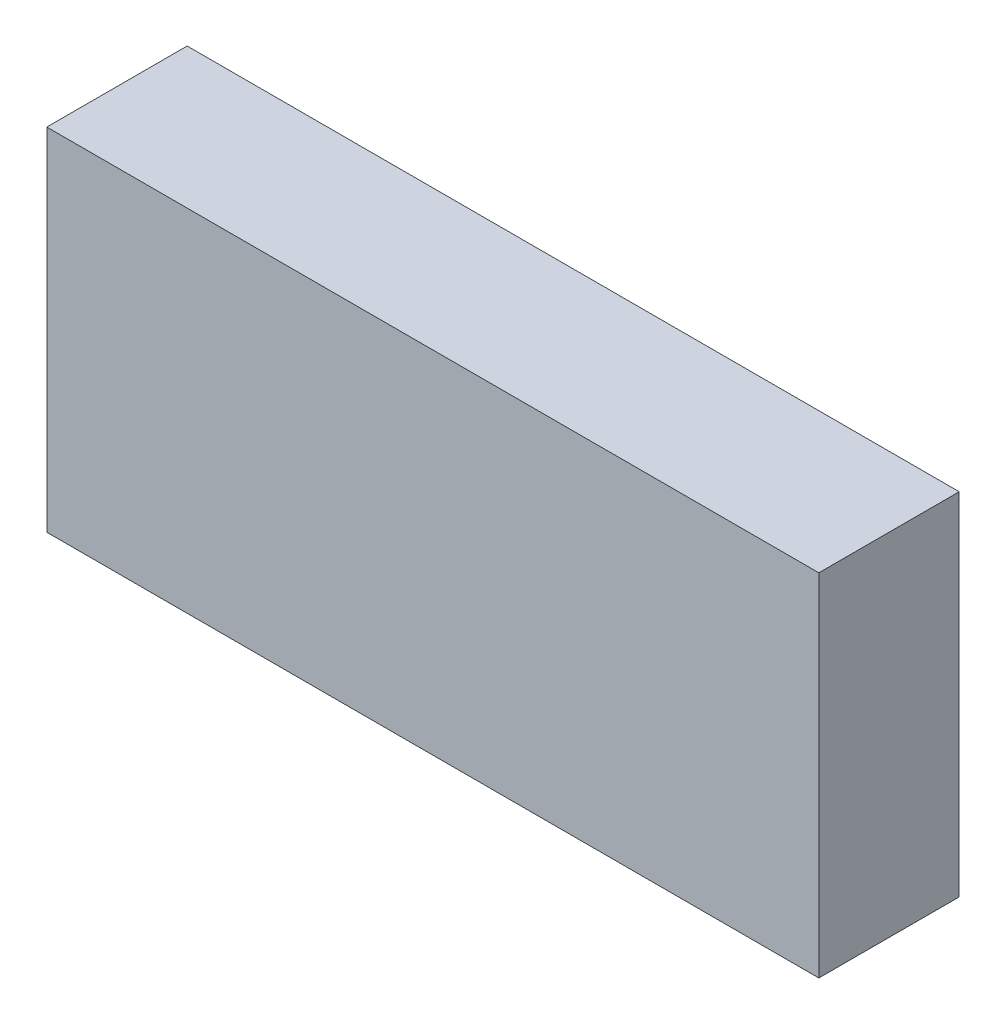
SolidWorks part; units mm, degrees
ref_plane "Front Plane" through (0, 0, 0) normal (0, 0, 1) x (1, 0, 0)
ref_plane "Top Plane" through (0, 0, 0) normal (0, 1, 0) x (1, 0, 0)
ref_plane "Right Plane" through (0, 0, 0) normal (1, 0, 0) x (0, 0, -1)
sketch "Sketch1" plane through (0, 0, 0) normal (0, 1, 0) x (1, 0, 0)
  line L1 (-19.5, 77.5) -> (19.5, 77.5)
  line L2 (-19.5, 77.5) -> (-19.5, -77.5)
  line L3 (-19.5, -77.5) -> (19.5, -77.5)
  line L4 (19.5, 77.5) -> (19.5, -77.5)
  line L5 (-19.5, 77.5) -> (19.5, -77.5) construction
  line L6 (-19.5, -77.5) -> (19.5, 77.5) construction
  point P0 (0, 0)
  dimension "D1" = 39
  dimension "D2" = 155
extrude "Boss-Extrude1" add sketch "Sketch1" along normal blind 2
sketch "Sketch2" plane through (0, 2, 0) normal (0, 1, 0) x (1, 0, 0)
  line L0 (-17.5, -75.5) -> (-17.5, -77.5)
  line L1 (-19.5, 77.5) -> (19.5, 77.5)
  line L2 (-19.5, 77.5) -> (-19.5, -77.5)
  line L3 (-19.5, -77.5) -> (19.5, -77.5)
  line L4 (19.5, 77.5) -> (19.5, -77.5)
  line L5 (-17.5, 75.5) -> (17.5, 75.5)
  line L6 (-17.5, 75.5) -> (-17.5, -75.5)
  line L7 (-17.5, -75.5) -> (17.5, -75.5)
  line L8 (17.5, 75.5) -> (17.5, -75.5)
  line L9 (-17.5, 75.5) -> (17.5, -75.5) construction
  line L10 (-17.5, -75.5) -> (17.5, 75.5) construction
  line L11 (17.5, -75.5) -> (17.5, -77.5)
  point P6 (0, 0)
  line M9 (19.5, -77.5) -> (19.5, 77.5)
  line M10 (19.5, 77.5) -> (-19.5, 77.5)
  line M11 (-19.5, 77.5) -> (-19.5, -77.5)
  line M12 (-19.5, -77.5) -> (19.5, -77.5)
  dimension "D1" = 2
  dimension "D2" = 2
extrude "Boss-Extrude2" add sketch "Sketch2" along normal blind 38 contours L8 L11 L3 L0 L6 L5 M9 M10 M11 M12 region at (-19.0983, 2, 76.5)
sketch "Sketch3" plane through (0, 2, 0) normal (0, 1, 0) x (1, 0, 0)
  line L0 (-17.5, 75.5) -> (-17.5, -77.5) construction
  line L1 (-17.5, -77.5) -> (-15.5, -77.5)
  line L2 (-17.5, -77.5) -> (-17.5, -75.5)
  line L3 (-17.5, -75.5) -> (-15.5, -75.5)
  line L4 (-15.5, -77.5) -> (-15.5, -75.5)
  line L5 (-17.5, -73.3) -> (-15.5, -73.3)
  line L6 (-17.5, -73.3) -> (-17.5, -71.3)
  line L7 (-17.5, -71.3) -> (-15.5, -71.3)
  line L8 (-15.5, -73.3) -> (-15.5, -71.3)
  line L9 (17.5, 75.5) -> (17.5, -77.5) construction
  line L10 (17.5, -77.5) -> (15.5, -77.5)
  line L11 (17.5, -77.5) -> (17.5, -75.5)
  line L12 (17.5, -75.5) -> (15.5, -75.5)
  line L13 (15.5, -77.5) -> (15.5, -75.5)
  line L14 (17.5, -73.3) -> (15.5, -73.3)
  line L15 (17.5, -73.3) -> (17.5, -71.3)
  line L16 (17.5, -71.3) -> (15.5, -71.3)
  line L17 (15.5, -73.3) -> (15.5, -71.3)
  line L18 (15.5, -75.5) -> (15.5, -73.3) construction
  line L19 (-15.5, -73.3) -> (15.5, -73.3) construction
  line L20 (-15.5, -75.5) -> (-15.5, -73.3) construction
  line L21 (-15.5, -75.5) -> (15.5, -75.5) construction
  line L22 (15.5, -71.3) -> (-15.5, -71.3) construction
  dimension "D1" = 2
  dimension "D2" = 2
  dimension "D3" = 2.2
  dimension "D4" = 2
extrude "Boss-Extrude3" add sketch "Sketch3" along normal up to surface (38 mm away) up to face at (0, 40, 0.5)
sketch "Sketch4" plane through (0, 0, -75.5) normal (0, 0, 1) x (1, 0, 0)
  line L0 (-17.5, 40) -> (-15.5, 40)
  line L1 (-17.5, 40) -> (17.5, 40) construction
  line L2 (-15.5, 40) -> (-15.5, 38)
  line L3 (-15.5, 38) -> (-17.5, 38)
  line L5 (-17.5, 38) -> (-17.5, 40)
  line L7 (-17.5, 40) -> (-17.5, 2) construction
  line L8 (-15.5, 33.8) -> (-17.5, 31.8)
  line L9 (-17.5, 31.8) -> (-17.5, 35.8)
  line L10 (-15.5, 33.8) -> (-15.5, 35.8)
  line L11 (-15.5, 35.8) -> (-17.5, 35.8)
  line L12 (0, 0) -> (0, 40) construction
  line L13 (15.5, 35.8) -> (17.5, 35.8)
  line L14 (15.5, 33.8) -> (15.5, 35.8)
  line L15 (17.5, 31.8) -> (17.5, 35.8)
  line L16 (15.5, 33.8) -> (17.5, 31.8)
  line L17 (17.5, 38) -> (17.5, 40)
  line L18 (15.5, 38) -> (17.5, 38)
  line L19 (15.5, 40) -> (15.5, 38)
  line L20 (17.5, 40) -> (15.5, 40)
  dimension "D1" = 2
  dimension "D2" = 2
  dimension "D3" = 45
  dimension "D4" = 2.2
  dimension "D5" = 2
extrude "Boss-Extrude4" add sketch "Sketch4" along normal up to surface (153 mm away) up to face at (0, 20.5, 77.5)
sketch "Sketch5" plane through (0, 2, 0) normal (0, 1, 0) x (1, 0, 0)
  line L1 (-15.5, -77.5) -> (15.5, -77.5)
  line L2 (-15.5, -77.5) -> (-15.5, -75.5)
  line L3 (-15.5, -75.5) -> (15.5, -75.5)
  line L4 (15.5, -77.5) -> (15.5, -75.5)
  line L5 (-15.5, -71.3) -> (15.5, -71.3)
  line L6 (-15.5, -71.3) -> (-15.5, -73.3)
  line L7 (-15.5, -73.3) -> (15.5, -73.3)
  line L8 (15.5, -71.3) -> (15.5, -73.3)
sketch "Sketch6" plane through (0, 0, -75.5) normal (0, 0, 1) x (1, 0, 0)
  line L0 (-17.5, 38) -> (-15.5, 38) construction
  line L1 (-17.5, 38) -> (17.5, 38)
  line L2 (-17.5, 38) -> (-17.5, 35.8)
  line L3 (-17.5, 35.8) -> (17.5, 35.8)
  line L4 (17.5, 38) -> (17.5, 35.8)
  line L5 (-17.5, 38) -> (-17.5, 35.8) construction
  line L6 (-15.5, 35.8) -> (-17.5, 35.8) construction
extrude "Cut-Extrude1" cut sketch "Sketch6" along normal through all
sketch "Sketch7" plane through (0, 2, 0) normal (0, 1, 0) x (1, 0, 0)
  line L1 (-17.5, -75.5) -> (17.5, -75.5)
  line L2 (-17.5, -75.5) -> (-17.5, -73.3)
  line L3 (-17.5, -73.3) -> (17.5, -73.3)
  line L4 (17.5, -75.5) -> (17.5, -73.3)
extrude "Cut-Extrude2" cut sketch "Sketch7" along normal through all
extrude "Boss-Extrude5" add sketch "Sketch5" along normal blind 2
sketch "Sketch8" plane through (0, 0, 0) normal (1, 0, 0) x (0, 0, -1)
  line L0 (75.5, 40) -> (73.5, 40)
  line L1 (-73.3, 40) -> (75.5, 40) construction
  line L2 (73.5, 40) -> (73.5, 38)
  line L3 (-73.3, 38) -> (75.5, 38) construction
  line L4 (73.5, 38) -> (75.5, 38)
  line L5 (75.5, 38) -> (75.5, 40)
  line L6 (75.5, 35.8) -> (73.5, 35.8)
  line L7 (-73.3, 35.8) -> (75.5, 35.8) construction
  line L8 (73.5, 35.8) -> (73.5, 33.8)
  line L9 (-71.3, 33.8) -> (75.5, 33.8) construction
  line L10 (73.5, 33.8) -> (75.5, 31.8)
  line L11 (75.5, 31.8) -> (75.5, 35.8)
  dimension "D1" = 2
extrude "Boss-Extrude6" add sketch "Sketch8" along normal up to surface and the other way up to surface up to face at (17.5, 16.9, -2.1) other way up to face at (-17.5, 16.9, -2.1)
sketch "Sketch10" plane through (-17.5, 0, 0) normal (1, 0, 0) x (0, 0, -1)
  line L1 (-75.5, 35.8) -> (-77.5, 35.8)
  line L2 (-75.5, 35.8) -> (-75.5, 38)
  line L3 (-75.5, 38) -> (-77.5, 38)
  line L4 (-77.5, 35.8) -> (-77.5, 38)
  line L5 (-73.3, 40) -> (-75.5, 40)
  line L6 (-73.3, 40) -> (-73.3, 38)
  line L7 (-73.3, 38) -> (-75.5, 38)
  line L8 (-75.5, 40) -> (-75.5, 38)
  line M1 (-75.5, 40) -> (-75.5, 38)
  line M2 (-75.5, 38) -> (-77.5, 38)
  line M3 (-77.5, 38) -> (-77.5, 35.8)
  line M4 (-77.5, 35.8) -> (-75.5, 35.8)
  line M11 (-73.3, 38) -> (-73.3, 40)
  line M12 (-73.3, 40) -> (-75.5, 40)
extrude "Boss-Extrude8" add sketch "Sketch10" along normal up to surface (2 mm away) contours L2 M4 M2 M3 | L7 M11 M12 M1 region at (-17.5, 39, 74.4) region at (-17.5, 36.9, 76.5) up to face at (-15.5, 39, -0.1)
sketch "Sketch11" plane through (17.5, 0, 0) normal (-1, 0, 0) x (0, 0, 1)
  line L1 (75.5, 35.8) -> (77.5, 35.8)
  line L2 (75.5, 35.8) -> (75.5, 38)
  line L3 (75.5, 38) -> (77.5, 38)
  line L4 (77.5, 35.8) -> (77.5, 38)
  line L5 (73.3, 40) -> (75.5, 40)
  line L6 (73.3, 40) -> (73.3, 38)
  line L7 (73.3, 38) -> (75.5, 38)
  line L8 (75.5, 40) -> (75.5, 38)
  line M2 (75.5, 35.8) -> (77.5, 35.8)
  line M3 (77.5, 35.8) -> (77.5, 38)
  line M4 (77.5, 38) -> (75.5, 38)
  line M5 (75.5, 38) -> (75.5, 40)
  line M6 (75.5, 40) -> (73.3, 40)
  line M7 (73.3, 40) -> (73.3, 38)
extrude "Boss-Extrude9" add sketch "Sketch11" along normal up to surface (2 mm away) contours L2 M2 M3 M4 | L7 M7 M5 M6 region at (17.5, 36.9, 76.5) region at (17.5, 39, 74.4) up to face at (15.5, 39, -0.1)
fillet "Fillet2" radius 2.5 17 edges at (-17.5, 16.9, 71.3) (17.5, 16.9, 71.3) (19.5, 20, 77.5) (-19.5, 20, 77.5) (-19.5, 20, -77.5) (-17.5, 16.9, -75.5) (17.5, 16.9, -75.5) (19.5, 20, -77.5) (-19.5, 40, 0) (0, 40, -77.5) (19.5, 40, 0) (0, 0, -77.5) (0, 0, 77.5) (-19.5, 0, 0) (19.5, 0, 0) (-17.5, 40, 77.5) (17.5, 40, 77.5)
sketch "Sketch13" plane through (0, 0, -77.5) normal (0, 0, -1) x (-1, 0, 0)
  line L0 (15.5, 37.5) -> (15.5, 4) construction
  line L1 (-15.5, 7) -> (15.5, 7)
  line L2 (-15.5, 7) -> (-15.5, 4)
  line L3 (-15.5, 4) -> (15.5, 4)
  line L4 (15.5, 7) -> (15.5, 4)
  dimension "D1" = 3
sketch "Sketch14" plane through (0, 0, -75.5) normal (0, 0, 1) x (1, 0, 0)
  line L1 (-18.25, 9) -> (18.25, 9)
  line L2 (-18.25, 9) -> (-18.25, 1.25)
  line L3 (-18.25, 1.25) -> (18.25, 1.25)
  line L4 (18.25, 9) -> (18.25, 1.25)
  line L5 (15.5, 7) -> (-15.5, 7) construction
  line L7 (17, 0) -> (17, 2.5) construction
  line L8 (19.5, 2.5) -> (17, 2.5) construction
  line L10 (-19.5, 2.5) -> (-17, 2.5) construction
  point P20 (17, 1.25)
  point P23 (18.25, 2.5)
  point P26 (-18.25, 2.5)
  dimension "D1" = 2
extrude "Boss-Extrude10" add sketch "Sketch14" along normal blind 2
extrude "Cut-Extrude4" cut sketch "Sketch13" against normal blind 2
fillet "Fillet3" radius 2 1 edges at (0, 9, -73.5)
fillet "Fillet4" radius 0.5 12 edges at (0, 4, -77.5) (0, 7, -77.5) (15.5, 7, -76.5) (15.5, 4, -76.5) (15.5, 5.5, -77.5) (-15.5, 4, -76.5) (-15.5, 7, -76.5) (-15.5, 5.5, -77.5) (0, 7, -75.5) (-15.5, 5.5, -75.5) (0, 4, -75.5) (15.5, 5.5, -75.5)
sketch "Sketch15" plane through (0, 0, 0) normal (0, -1, 0) x (1, 0, 0)
  line L0 (0, 77.5) -> (0, 0) construction
  line L1 (-17, 77.5) -> (17, 77.5) construction
  line L2 (0, 0) -> (0, -77.5) construction
  line L4 (17, -77.5) -> (-17, -77.5) construction
  circle A0 centre (0, 38.75) radius 5.1
  circle A1 centre (0, -38.75) radius 5.1
  dimension "D1" = 10.2
extrude "Cut-Extrude5" cut sketch "Sketch15" against normal through all
sketch "Sketch16" plane through (0, 2, 0) normal (0, 1, 0) x (1, 0, 0)
  circle A0 centre (0, 38.75) radius 7.1
  circle A1 centre (0, -38.75) radius 7.1
  circle A2 centre (0, 38.75) radius 5.1 construction
  dimension "D1" = 2
extrude "Boss-Extrude11" add sketch "Sketch16" along normal blind 1
fillet "Fillet5" radius 0.5 4 edges at (0, 2, 45.85) (0, 2, -31.65) (0, 3, 45.85) (0, 3, -31.65)
fillet "Fillet7" radius 0.5 8 edges at (15.5, 40, 0.75) (15.5, 39.2678, 76.7678) (-15.5, 40, 0.75) (-15.5, 39.2678, 76.7678) (0, 40, -73.5) (15.5, 20.75, 77.5) (-15.5, 20.75, 77.5) (0, 4, 77.5)
sketch "Sketch17" plane through (0, 0, 0) normal (0, -1, 0) x (1, 0, 0)
  line L0 (-17, -77.5) -> (-17, 70.3)
  line L1 (-17, -77.5) -> (17, -77.5)
  line L2 (17, -77.5) -> (17, 70.3)
  line L3 (17, -75) -> (17, 75) construction
  line L5 (17, 70.3) -> (15, 71.3)
  line L6 (15, 71.3) -> (15, 77.5)
  line L7 (15, 77.5) -> (-15, 77.5)
  line L8 (-15, 77.5) -> (-15, 71.3)
  line L9 (-15, 71.3) -> (-17, 70.3)
  line L10 (-17, 75) -> (-17, -75) construction
  line L12 (-15, 71.3) -> (15, 71.3) construction
  line L13 (17, 70.3) -> (-17, 70.3) construction
  line L14 (0, 71.3) -> (0, 77.5) construction
  line L15 (-17, 77.5) -> (17, 77.5) construction
  arc A0 (-19.5, -75) -> (-17, -77.5) centre (-17, -75) ccw construction
  dimension "D1" = 1
  dimension "D2" = 30
  dimension "D3" = 6.2
extrude "Cut-Extrude6" cut sketch "Sketch17" against normal blind 6
sketch "Sketch18" plane through (0, 0, 0) normal (0, 0, 1) x (1, 0, 0)
  line L0 (15, 9) -> (-15, 9) construction
  line L1 (-14.5, 9) -> (14.5, 9)
  line L2 (-14.5, 9) -> (-14.5, 6)
  line L3 (-14.5, 6) -> (14.5, 6)
  line L4 (14.5, 9) -> (14.5, 6)
  line L5 (-17, 6) -> (17, 6) construction
  line L6 (0, 6) -> (0, 0) construction
  dimension "D1" = 29
extrude "Cut-Extrude8" cut sketch "Sketch18" against normal through all
sketch "Sketch20" plane through (0, 0, 0) normal (0, 0, 1) x (1, 0, 0)
  line L0 (-16, 40) -> (16, 40) construction
  line L1 (-19.5, 40) -> (-14.5, 40)
  line L2 (-19.5, 40) -> (-19.5, 0)
  line L3 (-19.5, 0) -> (-14.5, 0)
  line L4 (-14.5, 40) -> (-14.5, 0)
  line L5 (-14.5, 6) -> (14.5, 6)
  line L6 (-14.5, 6) -> (-14.5, 40)
  line L7 (-14.5, 40) -> (14.5, 40)
  line L8 (14.5, 6) -> (14.5, 40)
  line L9 (14.5, 40) -> (19.5, 40)
  line L10 (14.5, 40) -> (14.5, 0)
  line L11 (14.5, 0) -> (19.5, 0)
  line L12 (19.5, 40) -> (19.5, 0)
  line L13 (-15, 0) -> (-17, 0) construction
  line L14 (-19.5, 2.5) -> (-19.5, 37.5) construction
  line L15 (17, 0) -> (15, 0) construction
  line L16 (19.5, 37.5) -> (19.5, 2.5) construction
extrude "Cut-Extrude11" cut sketch "Sketch20" against normal through all both and the other way through all contours L12 L9 L8 L10 L11 | L1 L2 L3 L4 region at (17, 20, 0)
sketch "Sketch21" plane through (0, 0, 0) normal (0, 0, 1) x (1, 0, 0)
  line L0 (14.5, 40) -> (-14.5, 40) construction
  line L1 (-14.5, 9) -> (14.5, 9)
  line L2 (-14.5, 9) -> (-14.5, 40)
  line L3 (-14.5, 40) -> (14.5, 40)
  line L4 (14.5, 9) -> (14.5, 40)
  line L5 (-14.5, 9) -> (14.5, 40) construction
  line L6 (-14.5, 40) -> (14.5, 9) construction
  line L8 (-5.5, 9) -> (5.5, 9)
  line L9 (-5.5, 9) -> (-5.5, 40)
  line L10 (-5.5, 40) -> (5.5, 40)
  line L11 (5.5, 9) -> (5.5, 40)
  line L12 (-5.5, 9) -> (5.5, 40) construction
  line L13 (-5.5, 40) -> (5.5, 9) construction
  point P0 (0, 24.5)
  point P7 (0, 24.5)
  dimension "D1" = 11
extrude "Cut-Extrude12" cut sketch "Sketch21" against normal through all contours L1 L9 L3 L2 | L11 L1 L4 L3 region at (-10, 24.5, 0) region at (10, 24.5, 0)
sketch "Sketch22" plane through (0, 0, -75.5) normal (0, 0, 1) x (1, 0, 0)
  line L1 (-5.5, 40) -> (5.5, 40)
  line L2 (-5.5, 40) -> (-5.5, 31.8)
  line L3 (-5.5, 31.8) -> (5.5, 31.8)
  line L4 (5.5, 40) -> (5.5, 31.8)
  line L5 (-5.5, 9) -> (5.5, 9)
  line L6 (-5.5, 9) -> (-5.5, 31.8)
  line L7 (-5.5, 31.8) -> (5.5, 31.8)
  line L8 (5.5, 9) -> (5.5, 31.8)
  line M1 (5.5, 31.8) -> (-5.5, 31.8)
extrude "Cut-Extrude13" cut sketch "Sketch22" against normal through all both and the other way through all contours L4 L1 L2 M1 region at (0, 35.9, -75.5)
sketch "Sketch23" plane through (0, 0, -75.5) normal (0, 0, 1) x (1, 0, 0)
  line L0 (5.5, 31.8) -> (5.5, 9) construction
  line L1 (-5.5, 9) -> (5.5, 9)
  line L2 (-5.5, 9) -> (-5.5, 26.8)
  line L3 (-5.5, 26.8) -> (5.5, 26.8)
  line L4 (5.5, 9) -> (5.5, 26.8)
  line L5 (5.5, 31.8) -> (-5.5, 31.8) construction
  dimension "D1" = 5
extrude "Cut-Extrude14" cut sketch "Sketch23" against normal through all
